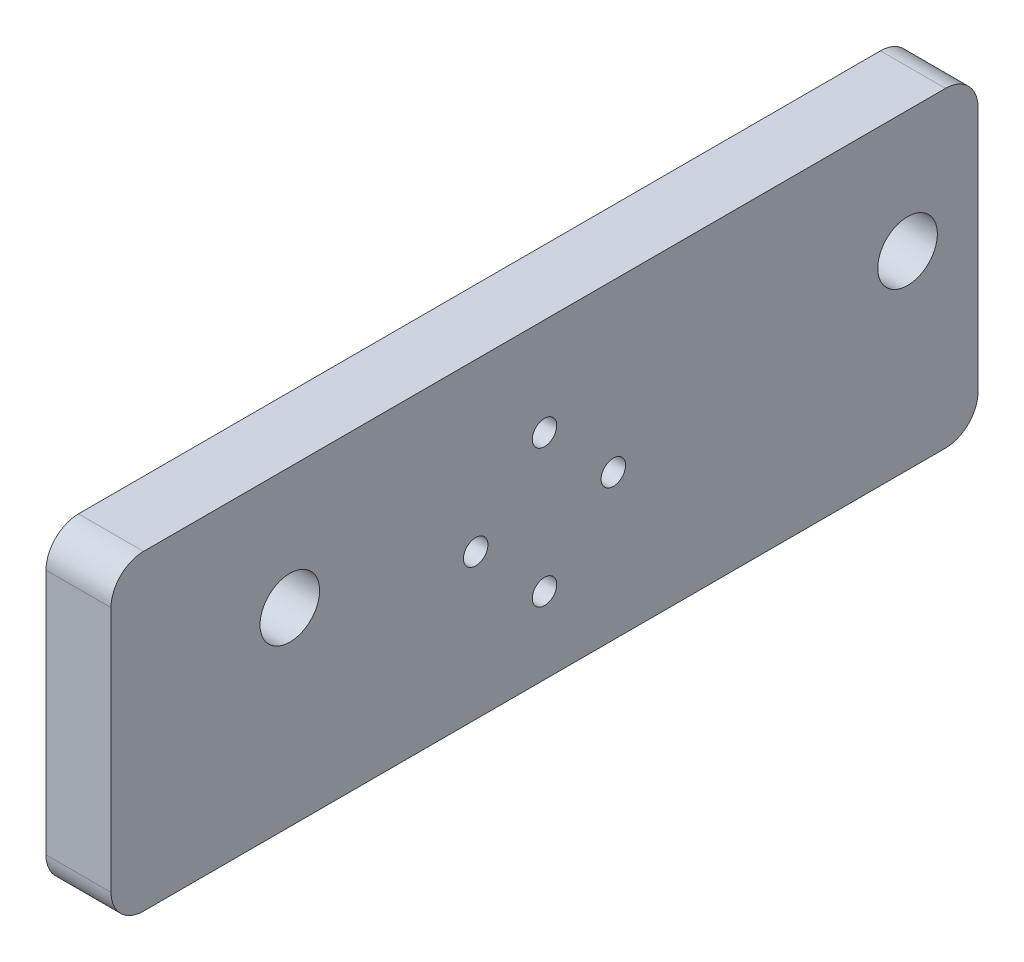
SolidWorks part; units mm, degrees
ref_plane "Front Plane" through (0, 0, 0) normal (0, 0, 1) x (1, 0, 0)
ref_plane "Top Plane" through (0, 0, 0) normal (0, 1, 0) x (1, 0, 0)
ref_plane "Right Plane" through (0, 0, 0) normal (1, 0, 0) x (0, 0, -1)
sketch "Sketch1" plane through (0, 0, 0) normal (1, 0, 0) x (0, 0, -1)
  line L0 (-6.35, -0.975) -> (6.35, -0.975) construction
  line L1 (-40, 14.375) -> (40, 14.375)
  line L2 (-40, 14.375) -> (-40, -14.375)
  line L3 (-40, -14.375) -> (40, -14.375)
  line L4 (40, 14.375) -> (40, -14.375)
  line L5 (-40, 14.375) -> (40, -14.375) construction
  line L6 (-40, -14.375) -> (40, 14.375) construction
  line L7 (0, 5.375) -> (0, -7.325) construction
  point P0 (0, 0)
  point P6 (-23.5, 3.125)
  point P7 (33.5, 3.125)
  point P8 (-6.35, -0.975)
  point P9 (6.35, -0.975)
  point P12 (0, -0.975)
  point P13 (0, 5.375)
  point P14 (0, -7.325)
  dimension "D1" = 28.75
  dimension "D2" = 80
  dimension "D3" = 11.25
  dimension "D4" = 16.5
  dimension "D5" = 6.5
  dimension "D6" = 13.4
  dimension "D7" = 12.7
  dimension "D8" = 12.7
extrude "Boss-Extrude1" add sketch "Sketch1" along normal blind 6
hole_wizard "M5 Clearance Hole1" positions "Sketch3" profile "Sketch2" hole size "M5" standard "ANSI Metric" end condition through all
sketch "Sketch3" plane through (0, 0, 0) normal (-1, 0, 0) x (0, 0, 1)
  point P0 (-33.5, 3.125)
  point P3 (23.5, 3.125)
sketch "Sketch2" plane through (0, 3.125, -33.5) normal (0, 1, 0) x (0, 0, 1)
  line L0 (0, 0) -> (0, 6)
  line L1 (0, 6) -> (2.75, 6)
  line L2 (2.75, 6) -> (2.75, 0)
  line L5 (2.75, 0) -> (0, 0)
  line L11 (0, -6.35) -> (0, 107.95) construction
  dimension "Thru Hole Dia." = 5.5
  dimension "Thru Hole Depth" = 6
hole_wizard "#2 Clearance Hole1" positions "Sketch8" profile "Sketch7" hole size "#2" standard "ANSI Inch" end condition through all
sketch "Sketch8" plane through (0, 0, 0) normal (-1, 0, 0) x (0, 0, 1)
  point P0 (-6.35, -0.975)
  point P3 (6.35, -0.975)
  point P7 (0, -7.325)
  point P9 (0, 5.375)
sketch "Sketch7" plane through (0, -0.975, -6.35) normal (0, 1, 0) x (0, 0, 1)
  line L0 (0, 0) -> (0, 6)
  line L1 (0, 6) -> (1.1303, 6)
  line L2 (1.1303, 6) -> (1.1303, 0)
  line L5 (1.1303, 0) -> (0, 0)
  line L11 (0, -6.35) -> (0, 107.95) construction
  dimension "Thru Hole Dia." = 2.2606
  dimension "Thru Hole Depth" = 6
sketch "Sketch9" plane through (6, 0, 0) normal (1, 0, 0) x (0, 0, -1)
  line L0 (-6.35, -0.975) -> (6.35, -0.975) construction
  line L1 (-10.35, -4.975) -> (10.35, -4.975)
  line L2 (-10.35, -4.975) -> (-10.35, 3.025)
  line L3 (-10.35, 3.025) -> (10.35, 3.025)
  line L4 (10.35, -4.975) -> (10.35, 3.025)
  line L5 (-10.35, -4.975) -> (10.35, 3.025) construction
  line L6 (-10.35, 3.025) -> (10.35, -4.975) construction
  point P0 (0, -0.975)
  dimension "D1" = 4
  dimension "D2" = 4
fillet "Fillet2" radius 3 4 edges at (3, -14.375, -40) (3, 14.375, -40) (3, 14.375, 40) (3, -14.375, 40)
sketch "Sketch10" plane through (0, 0, 0) normal (-1, 0, 0) x (0, 0, 1)
  circle A0 centre (0, -0.975) radius 2.75
  dimension "D1" = 5.5
extrude "Cut-Extrude1" [suppressed] cut sketch "Sketch10" against normal through all
